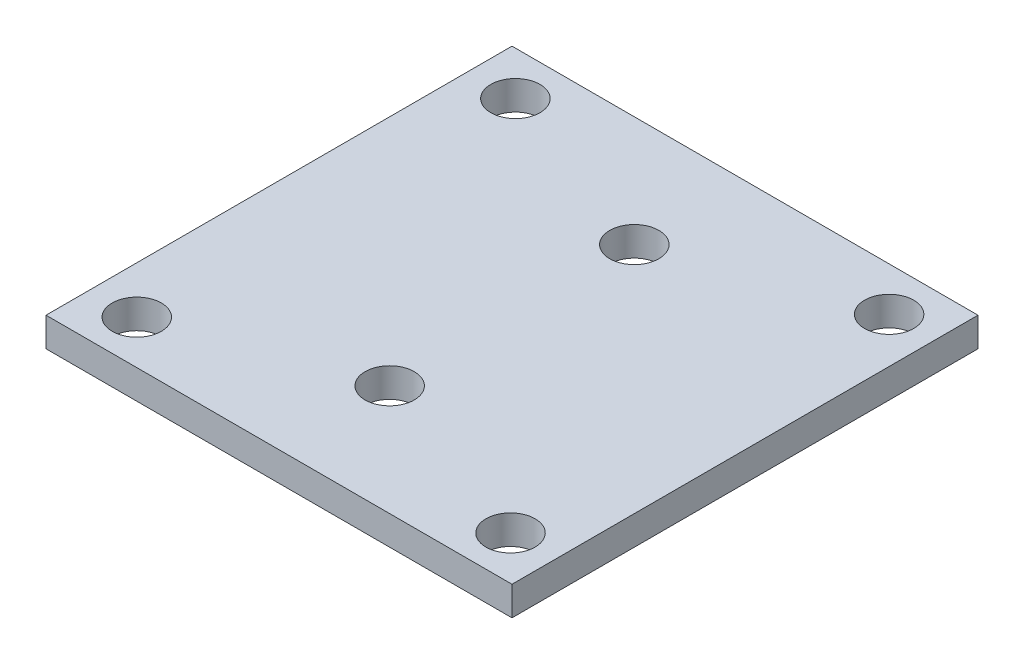
SolidWorks part; units mm, degrees
ref_plane "Front Plane" through (0, 0, 0) normal (0, 0, 1) x (1, 0, 0)
ref_plane "Top Plane" through (0, 0, 0) normal (0, 1, 0) x (1, 0, 0)
ref_plane "Right Plane" through (0, 0, 0) normal (1, 0, 0) x (0, 0, -1)
sketch "Sketch1" plane through (0, 0, 0) normal (0, 1, 0) x (1, 0, 0)
  line L1 (0, 0) -> (101.6, 0)
  line L2 (0, 0) -> (0, 101.6)
  line L3 (0, 101.6) -> (101.6, 101.6)
  line L4 (101.6, 0) -> (101.6, 101.6)
extrude "Boss-Extrude1" add sketch "Sketch1" along normal blind 6.35
hole_wizard "1/2-13 Tapped Hole1" positions "Sketch2" profile "Sketch3" tap size "1/2-13" standard "ANSI Inch" end condition through all
sketch "Sketch2" plane through (0, 6.35, 0) normal (0, 1, 0) x (1, 0, 0)
  line L0 (101.6, 101.6) -> (0, 101.6) construction
  line L1 (0, 0) -> (101.6, 0) construction
  point P0 (10.2661, 92.075)
  point P2 (91.7517, 9.525)
  point P11 (91.7517, 92.075)
  point P13 (10.2661, 9.525)
  dimension "D1" = 9.525
  dimension "D2" = 9.525
sketch "Sketch3" plane through (10.2661, 6.35, -92.075) normal (1, 0, 0) x (0, 0, 1)
  line L0 (0, 0) -> (0, 6.35)
  line L1 (0, 6.35) -> (5.3581, 6.35)
  line L2 (5.3581, 6.35) -> (5.3581, 0)
  line L5 (5.3581, 0) -> (0, 0)
  line L11 (0, -6.35) -> (0, 107.95) construction
  dimension "Thru Tap Drill Dia." = 10.7163
  dimension "Thru Tap Drill Depth" = 6.35
cosmetic thread "Hole Thread1"
cosmetic thread "Hole Thread2"
cosmetic thread "Hole Thread3"
cosmetic thread "Hole Thread4"
hole_wizard "1/2-13 Tapped Hole2" positions "Sketch12" profile "Sketch11" tap size "1/2-13" standard "ANSI Inch" end condition through all
sketch "Sketch12" plane through (0, 6.35, 0) normal (0, 1, 0) x (1, 0, 0)
  line L0 (101.6, 0) -> (101.6, 101.6) construction
  line L1 (101.6, 101.6) -> (0, 101.6) construction
  line L2 (0, 0) -> (101.6, 0) construction
  point P0 (50.8, 77.47)
  point P2 (50.8, 24.13)
  point P11 (50.8, 0)
  dimension "D1" = 50.8
  dimension "D2" = 50.8
  dimension "D3" = 24.13
  dimension "D4" = 24.13
sketch "Sketch11" plane through (50.8, 6.35, -77.47) normal (1, 0, 0) x (0, 0, 1)
  line L0 (0, 0) -> (0, 6.35)
  line L1 (0, 6.35) -> (5.3581, 6.35)
  line L2 (5.3581, 6.35) -> (5.3581, 0)
  line L5 (5.3581, 0) -> (0, 0)
  line L11 (0, -6.35) -> (0, 107.95) construction
  dimension "Thru Tap Drill Dia." = 10.7163
  dimension "Thru Tap Drill Depth" = 6.35
cosmetic thread "Hole Thread5"
cosmetic thread "Hole Thread6"
